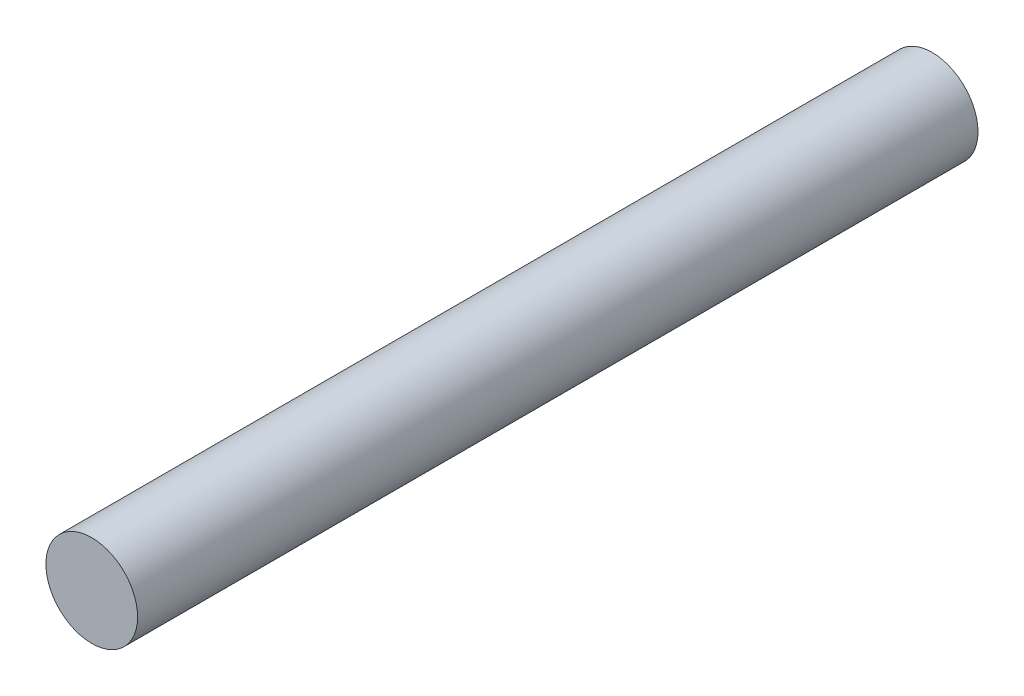
SolidWorks part; units mm, degrees
ref_plane "Front Plane" through (0, 0, 0) normal (0, 0, 1) x (1, 0, 0)
ref_plane "Top Plane" through (0, 0, 0) normal (0, 1, 0) x (1, 0, 0)
ref_plane "Right Plane" through (0, 0, 0) normal (1, 0, 0) x (0, 0, -1)
ref_axis "Axis1" through (0, 0, -2.5) along (0, 0, 1)
sketch "Sketch1" plane through (0, 0, 0) normal (0, 0, 1) x (1, 0, 0)
  circle A0 centre (0, 0) radius 3
  dimension "D1" = 6
extrude "Main" add sketch "Sketch1" along normal blind 55
